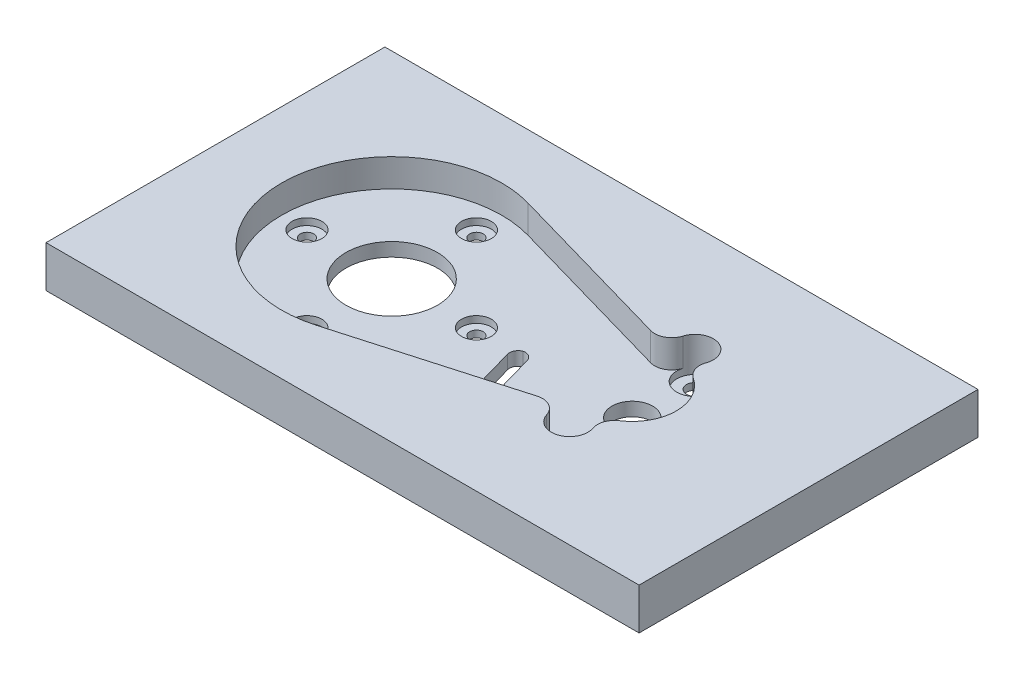
SolidWorks part; units mm, degrees
ref_plane "Front Plane" through (0, 0, 0) normal (0, 0, 1) x (1, 0, 0)
ref_plane "Top Plane" through (0, 0, 0) normal (0, 1, 0) x (1, 0, 0)
ref_plane "Right Plane" through (0, 0, 0) normal (1, 0, 0) x (0, 0, -1)
sketch "Sketch1" plane through (0, 0, 0) normal (0, 1, 0) x (1, 0, 0)
  line L0 (0, 73.0538) -> (0, -65.1274) construction
  line L1 (35.5, 6.365) -> (-28.5632, 24.502) construction
  line L2 (-70.6215, 0) -> (67.3742, 0) construction
  line L3 (35.5, -6.365) -> (-28.5632, -24.502) construction
  line L4 (4.5177, -15.1364) -> (0.1592, 0.2585)
  line L5 (0.1592, 0.2585) -> (4.6815, 1.5388)
  line L6 (4.6815, 1.5388) -> (9.04, -13.8561)
  line L7 (9.04, -13.8561) -> (9.5848, -15.7805)
  line L8 (9.5848, -15.7805) -> (5.0625, -17.0608)
  line L9 (5.0625, -17.0608) -> (4.5177, -15.1364)
  line L10 (-35.5, 0) -> (-60.5, 0) construction
  line L11 (-35.5, 0) -> (-35.5, 25) construction
  line L13 (-87.5, -50) -> (87.5, -50)
  line L14 (-87.5, -50) -> (-87.5, 50)
  line L15 (-87.5, 50) -> (87.5, 50)
  line L16 (87.5, -50) -> (87.5, 50)
  line L17 (-87.5, -50) -> (87.5, 50) construction
  line L18 (-87.5, 50) -> (87.5, -50) construction
  circle A0 centre (35.5, 0) radius 6
  circle A1 centre (-35.5, 0) radius 13.5
  circle A2 centre (-35.5, 0) radius 25.465 construction
  circle A3 centre (35.5, 0) radius 6.365 construction
  circle A4 centre (-60.5, 0) radius 2
  circle A5 centre (-35.5, 25) radius 2
  circle A6 centre (-10.5, 0) radius 2
  circle A7 centre (-35.5, -25) radius 2
  circle A8 centre (35.5, 18.5) radius 2.5
  circle A9 centre (35.5, -18.5) radius 2.5
  point P35 (0, 0)
  dimension "D1" = 12
  dimension "D2" = 27
  dimension "D5" = 50.93
  dimension "D6" = 12.73
  dimension "D12" = 4
  dimension "D19" = 5
  dimension "D3" = 71
  dimension "D4" = 35.5
  dimension "D7" = 90
  dimension "D8" = 27.5
  dimension "D9" = 4.7
  dimension "D10" = 16
  dimension "D11" = 2
  dimension "D13" = 25
  dimension "D15" = 90
  dimension "D16" = 25
  dimension "D17" = 175
  dimension "D18" = 100
  dimension "D20" = 18.5
  dimension "D14" = 4
extrude "Boss-Extrude1" add sketch "Sketch1" along normal blind 4
sketch "Sketch3" plane through (0, 4, 0) normal (0, 1, 0) x (1, 0, 0)
  line L0 (-26.5739, 31.2502) -> (39.0704, 12.5001)
  line L1 (-87.5, -50) -> (87.5, -50)
  line L2 (-87.5, -50) -> (-87.5, 50)
  line L3 (-87.5, 50) -> (87.5, 50)
  line L4 (87.5, -50) -> (87.5, 50)
  line L5 (-35.5, 0) -> (35.5, 0) construction
  line L6 (-26.5739, -31.2502) -> (39.0704, -12.5001)
  arc A0 (-26.5739, 31.2502) -> (-26.5739, -31.2502) centre (-35.5, 0) ccw
  arc A1 (39.0704, -12.5001) -> (39.0704, 12.5001) centre (35.5, 0) ccw
  dimension "D1" = 65
  dimension "D2" = 26
extrude "Boss-Extrude2" add sketch "Sketch3" along normal blind 8.25
sketch "Sketch6" plane through (0, 12.25, 0) normal (0, 1, 0) x (1, 0, 0)
  circle A0 centre (35.5, 18.5) radius 5.4
  circle A1 centre (35.5, -18.5) radius 5.4
  dimension "D1" = 10.8
extrude "Cut-Extrude2" cut sketch "Sketch6" against normal up to surface (8.25 mm away) up to face at (-1.7509, 4, 0)
fillet "Fillet1" radius 2.5 4 edges at (9.5848, 2, 15.7805) (5.0625, 2, 17.0608) (4.6815, 2, -1.5388) (0.1592, 2, -0.2585)
fillet "Fillet2" radius 5 4 edges at (36.5847, 8.125, 13.2101) (31.7849, 8.125, 14.5811) (36.5847, 8.125, -13.2101) (31.7849, 8.125, -14.5811)
sketch "Sketch2" plane through (0, 4, 0) normal (0, 1, 0) x (1, 0, 0)
  line L0 (29.5, 0) -> (41.5, 0) construction
  line L1 (35.5, 0) -> (35.5, -6) construction
  line L2 (35.5, 0) -> (35.5, 6) construction
  circle A0 centre (-35.5, 25) radius 4.4
  circle A1 centre (-10.5, 0) radius 4.4
  circle A2 centre (-35.5, -25) radius 4.4
  circle A3 centre (-60.5, 0) radius 4.4
  circle A4 centre (35.5, 0) radius 6 construction
  circle A7 centre (35.5, 18.5) radius 5.4
  circle A8 centre (35.5, -18.5) radius 5.4
  arc A9 (40.6003, 16.7261) -> (30.3389, 20.0883) centre (35.5, 18.5) ccw construction
  dimension "D1" = 8.8
extrude "Cut-Extrude1" cut sketch "Sketch2" against normal blind 2
sketch "Sketch7" plane through (0, 12.25, 0) normal (0, 1, 0) x (1, 0, 0)
  line L4 (-25.4754, -35.0964) -> (25.2854, -20.5975)
  line L5 (25.2854, 20.5975) -> (-25.4754, 35.0964)
  line L6 (-25.4754, -35.0964) -> (25.2854, -20.5975)
  line L7 (25.2854, 20.5975) -> (-25.4754, 35.0964)
  arc A16 (25.2854, 20.5975) -> (26.5158, 21.2649) centre (25.5601, 21.559) ccw
  arc A17 (44.3783, 15.412) -> (26.5158, 21.2649) centre (35.5, 18.5) ccw
  arc A18 (44.3783, 15.412) -> (44.7771, 14.2455) centre (45.3228, 15.0835) ccw
  arc A19 (44.7771, -14.2455) -> (44.3783, -15.412) centre (45.3228, -15.0835) ccw
  arc A20 (44.7771, -14.2455) -> (44.7771, 14.2455) centre (35.5, 0) ccw
  arc A21 (26.5158, -21.2649) -> (25.2854, -20.5975) centre (25.5601, -21.559) ccw
  arc A22 (26.5158, -21.2649) -> (44.3783, -15.412) centre (35.5, -18.5) ccw
  arc A23 (-25.4754, 35.0964) -> (-25.4754, -35.0964) centre (-35.5, 0) ccw
  arc A24 (25.2854, 20.5975) -> (26.5158, 21.2649) centre (25.5601, 21.559) ccw
  arc A25 (44.3783, 15.412) -> (26.5158, 21.2649) centre (35.5, 18.5) ccw
  arc A26 (44.3783, 15.412) -> (44.7771, 14.2455) centre (45.3228, 15.0835) ccw
  arc A27 (44.7771, -14.2455) -> (44.3783, -15.412) centre (45.3228, -15.0835) ccw
  arc A28 (44.7771, -14.2455) -> (44.7771, 14.2455) centre (35.5, 0) ccw
  arc A29 (26.5158, -21.2649) -> (25.2854, -20.5975) centre (25.5601, -21.559) ccw
  arc A30 (26.5158, -21.2649) -> (44.3783, -15.412) centre (35.5, -18.5) ccw
  arc A31 (-25.4754, 35.0964) -> (-25.4754, -35.0964) centre (-35.5, 0) ccw
  dimension "D1" = 4
extrude "Cut-Extrude4" [suppressed] cut sketch "Sketch7" against normal through all both and the other way through all flip side to cut
